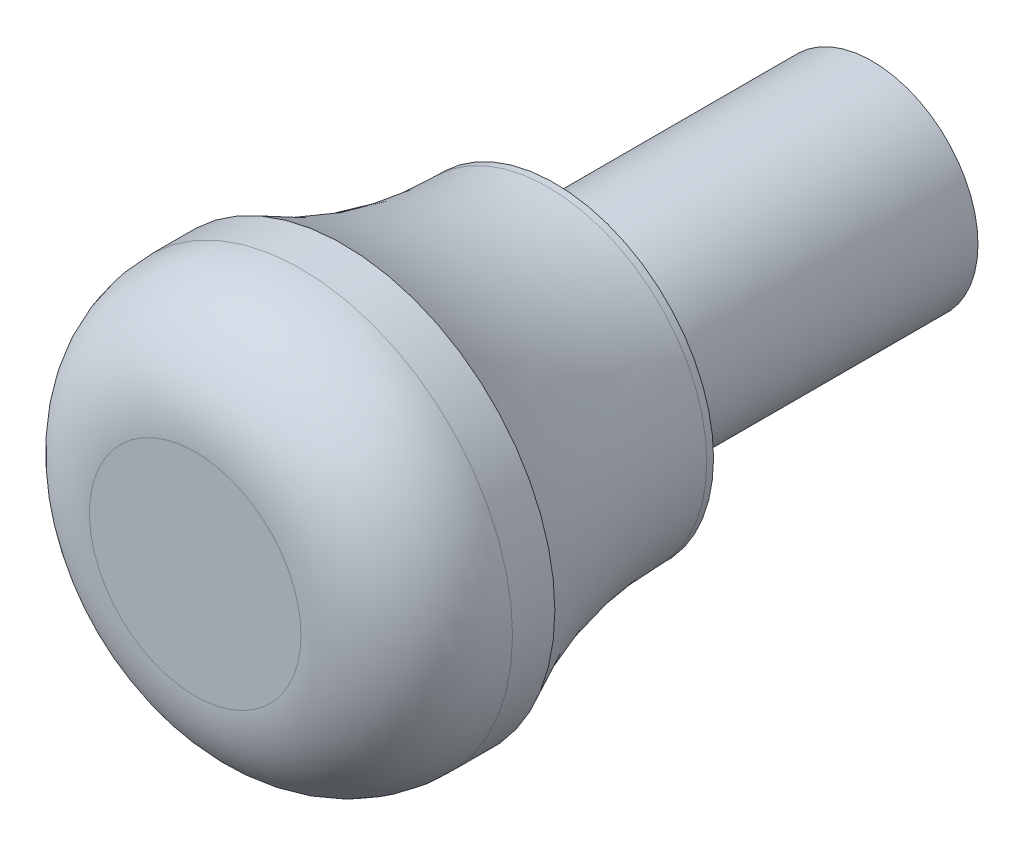
SolidWorks part; units mm, degrees
ref_plane "Front Plane" through (0, 0, 0) normal (0, 0, 1) x (1, 0, 0)
ref_plane "Top Plane" through (0, 0, 0) normal (0, 1, 0) x (1, 0, 0)
ref_plane "Right Plane" through (0, 0, 0) normal (1, 0, 0) x (0, 0, -1)
sketch "Sketch1" plane through (0, 0, 0) normal (0, 0, 1) x (1, 0, 0)
  circle A0 centre (0, 0) radius 5
  dimension "D1" = 10
extrude "Boss-Extrude1" add sketch "Sketch1" along normal blind 15
sketch "Sketch2" plane through (0, 0, 15) normal (0, 0, 1) x (1, 0, 0)
  circle A0 centre (0, 0) radius 7.5
extrude "Boss-Extrude2" add sketch "Sketch2" along normal blind 10
sketch "Sketch3" plane through (0, 0, 25) normal (0, 0, 1) x (1, 0, 0)
  circle A0 centre (0, 0) radius 10
extrude "Boss-Extrude3" add sketch "Sketch3" along normal blind 7
fillet "Fillet1" radius 20 1 edges at (7.5, 0, 25)
fillet "Fillet2" radius 5 1 edges at (10, 0, 32)
